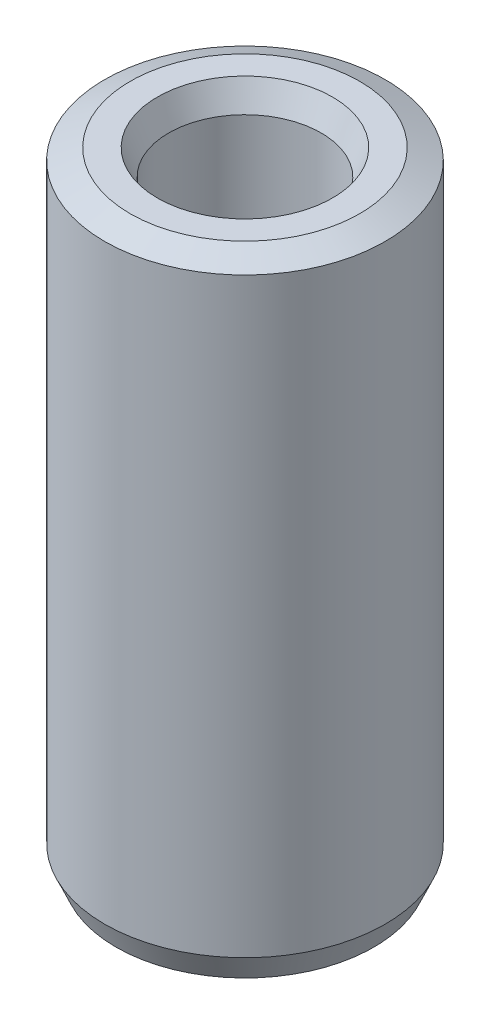
SolidWorks part; units mm, degrees
ref_plane "Front Plane" through (0, 0, 0) normal (0, 0, 1) x (1, 0, 0)
ref_plane "Top Plane" through (0, 0, 0) normal (0, 1, 0) x (1, 0, 0)
ref_plane "Right Plane" through (0, 0, 0) normal (1, 0, 0) x (0, 0, -1)
sketch "Sketch1" plane through (0, 0, 0) normal (0, 1, 0) x (1, 0, 0)
  circle A0 centre (0, 0) radius 7.5
  dimension "SLEEVE_OD" = 15
extrude "Boss-Extrude1" add sketch "Sketch1" along normal blind 33.5835
sketch "Sketch2" plane through (0, 0, 0) normal (0, 1, 0) x (1, 0, 0)
  circle A0 centre (0, 0) radius 4.0797
  dimension "BORE_D" = 8.1594
extrude "Cut-Extrude1" cut sketch "Sketch2" along normal through all
chamfer "Chamfer1" distance 0.6024 angle 66.18 4 edges at (0, 33.5835, 4.0797) (0, 0, 4.0797) (0, 0, 7.5) (0, 33.5835, 7.5) first distance on face at (0, 33.5835, 4.0797) first distance on face at (0, 0, 4.0797) first distance on face at (0, 33.5835, 7.5)
